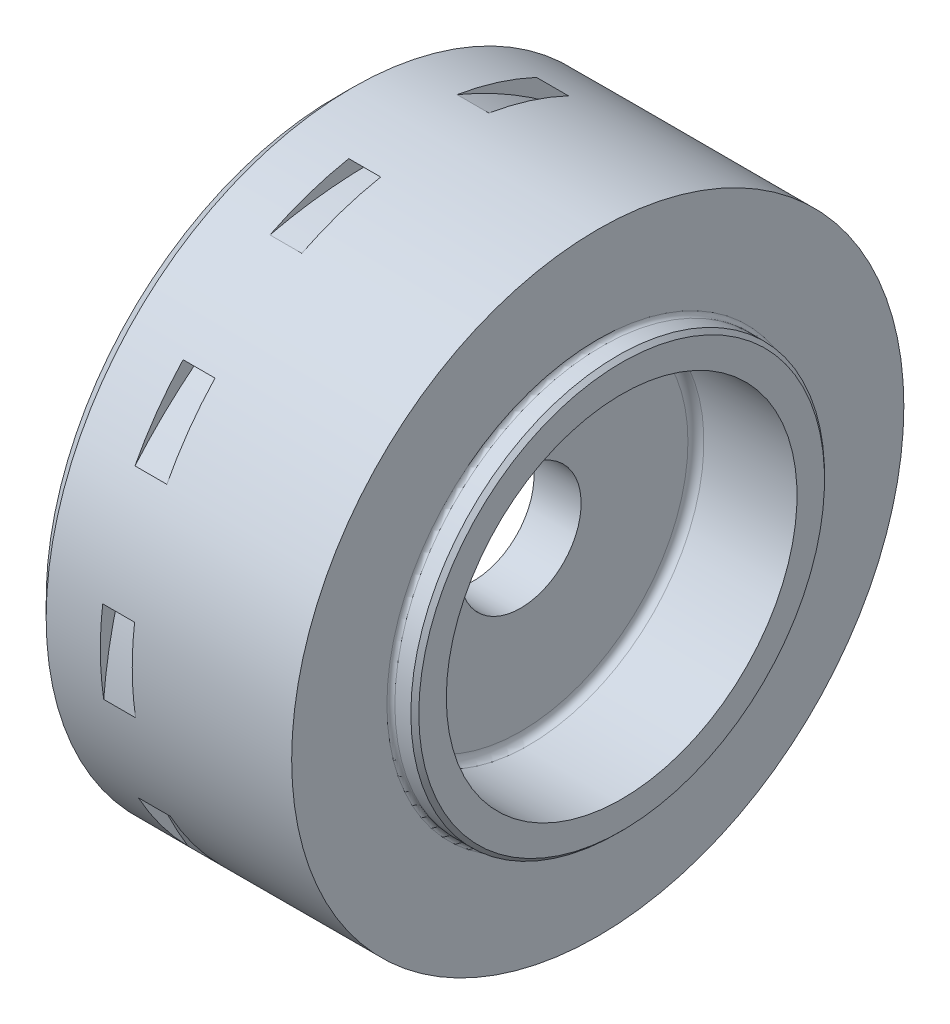
SolidWorks part; units mm, degrees
material "1.4006 (X10Cr13)"
ref_plane "Ebene vorne" through (0, 0, 0) normal (0, 0, 1) x (1, 0, 0)
ref_plane "Ebene oben" through (0, 0, 0) normal (0, 1, 0) x (1, 0, 0)
ref_plane "Ebene rechts" through (0, 0, 0) normal (1, 0, 0) x (0, 0, -1)
sketch "Skizze1" plane through (0, 0, 0) normal (0, 0, 1) x (1, 0, 0)
  line L1 (1.5217, 19.2) -> (9.3217, 19.2)
  line L7 (10.8217, 11) -> (4.4785, 11)
  line L10 (1.5217, 3.8) -> (1.5217, 15.65)
  line L13 (-0.6783, 19.2) -> (1.5217, 19.2)
  line L14 (-2.6783, 19.2) -> (-2.6783, 17.85)
  line L17 (-7.0783, 19.2) -> (-2.6783, 19.2)
  line L18 (-34.5672, 0) -> (67.8398, 0) construction
  line L19 (-0.6783, 17.85) -> (-0.6783, 19.2)
  line L20 (9.3217, 12.975) -> (9.3217, 19.2)
  line L23 (-2.6783, 17.85) -> (-4.6783, 15.83)
  line L24 (-0.6783, 17.85) -> (1.5217, 15.65)
  line L25 (-2.6783, 17.85) -> (-4.6783, 17.85) construction
  line L26 (-0.6783, 17.85) -> (2.5778, 17.85) construction
  line L28 (-4.6783, 15.83) -> (-7.0783, 15.83)
  line L31 (-7.0783, 19.2) -> (-7.0783, 15.83)
  line L32 (4.4785, 11) -> (4.4785, 3.8)
  line L33 (4.4785, 3.8) -> (1.5217, 3.8)
  line L34 (9.3217, 12.975) -> (10.5717, 12.975)
  line L35 (10.5717, 12.975) -> (10.8217, 12.725)
  line L36 (10.8217, 11) -> (10.8217, 12.725)
  dimension "D1" = 2
  dimension "D8" = 2
  dimension "D7" = 19.2
  dimension "D12" = 19.2
  dimension "D14" = 11
  dimension "D6" = 17.85
  dimension "D18" = 45
  dimension "D9" = 2.2
  dimension "D11" = 6.2
  dimension "D4" = 2.4
  dimension "D2" = 7.6
  dimension "D10" = 1.5217
  dimension "D13" = 0.18
  dimension "D15" = 2.9569
  dimension "D16" = 7.8
  dimension "D3" = 25.95
  dimension "D5" = 1.5
  dimension "D17" = 45
  dimension "D19" = 0.25
revolve "Rotation1" add sketch "Skizze1" angle 360 about L18
sketch "Skizze4" plane through (-2.6783, 0, 0) normal (1, 0, 0) x (0, 0, -1)
  line L0 (0, 17.85) -> (0, 0) construction
  line L1 (0, 17.85) -> (-6.0223, 17.85) construction
  line L2 (0, 17.85) -> (-1.5933, 17.9726) construction
  line L3 (-8.5638, 17.1843) -> (-3.0271, 18.4921) construction
  line L4 (-8.5638, 17.1843) -> (-6.5833, 18.1713) construction
  line L5 (-4.9, 17.1643) -> (-8.3476, 16.4608) construction
  line L6 (-4.9, 17.1643) -> (-7.2182, 16.5025) construction
  line L7 (-14.0099, 13.1287) -> (-11.9914, 14.4729) construction
  line L8 (-14.0099, 13.1287) -> (-10.3706, 17.0123) construction
  arc A1 (0, 17.85) -> (-8.5638, 17.1843) centre (-2.143, -10.0003) ccw
  circle A2 centre (-5.4295, 17.411) radius 0.325
  circle A7 centre (0, 0) radius 19.2
  circle A8 centre (0, 0) radius 17.85
  circle A10 centre (0, 0) radius 19.2 construction
  circle A11 centre (0, 0) radius 17.85 construction
  spline S0 degree 3 poles (-14.0099, 13.1287) (-13.3419, 13.5736) (-12.627, 13.8888) (-10.1528, 15.5184) knots 0 0 0 0 1 1 1 1
  spline S1 degree 3 poles (-4.9, 17.1643) (-6.0758, 16.9244) (-7.6743, 17.1566) (-10.1528, 15.5184) knots 0 0 0 0 1 1 1 1
  dimension "D1" = 4.4
  dimension "D2" = 13.2
  dimension "D3" = 0.65
  dimension "D4" = 4.4
  dimension "D5" = 13.2
  dimension "D8" = 4.9
  dimension "D6" = 5.4295
extrude "Aufsatz-Linear austragen1" add sketch "Skizze4" along direction (1, 0, 0) on the side of the normal up to surface (2 mm away)
pattern_circular "Kreismuster1" count 10 over 360 about axis through (-34.5672, 0, 0) along (-1, 0, 0) of "Aufsatz-Linear austragen1"
fillet "Verrundung1" radius 0.5 1 edges at (4.4785, 0, 11)
fillet "Verrundung2" radius 0.25 1 edges at (9.3217, 0, 12.975)
fillet "Verrundung3" radius 0.5 1 edges at (1.5217, 0, 15.65)
fillet "Verrundung4" radius 0.5 1 edges at (-4.6783, 0, 15.83)
fillet "Verrundung15" radius 0.1 10 edges at (-1.6783, -14.441, 10.492) (-1.6783, -17.85, 0) (-1.6783, -14.441, -10.492) (-1.6783, -5.516, -16.9764) (-1.6783, 5.516, -16.9764) (-1.6783, 14.441, -10.492) (-1.6783, 17.85, 0) (-1.6783, 14.441, 10.492) (-1.6783, 5.516, 16.9764) (-1.6783, -5.516, 16.9764)
ref_plane "Ebene1" through (-1.6783, 0, 0) normal (1, 0, 0) x (0, 0, -1)
chamfer "Chamfer1" distance 1 angle 45 2 edges at (-7.0783, 0, 15.83) (-7.0783, 0, 19.2)
equation "\"Thickness Diffuser\"= 2"
equation "\"Blade Number Diffusor\"= 10"
equation "\"b2s\"= 2"
equation "\"b3\"= 2"
equation "\"r3\"= 19.2"
equation "\"r2s\"= 17.85"
equation "\"D8@Skizze1\"=\"b3\""
equation "\"D1@Skizze1\"=\"b2s\""
equation "\"D1@Kreismuster1\"=\"Blade Number Diffusor\""
equation "\"D7@Skizze1\"=\"r3\""
equation "\"D12@Skizze1\"=\"r3\""
equation "\"D6@Skizze1\"=\"r2s\""
